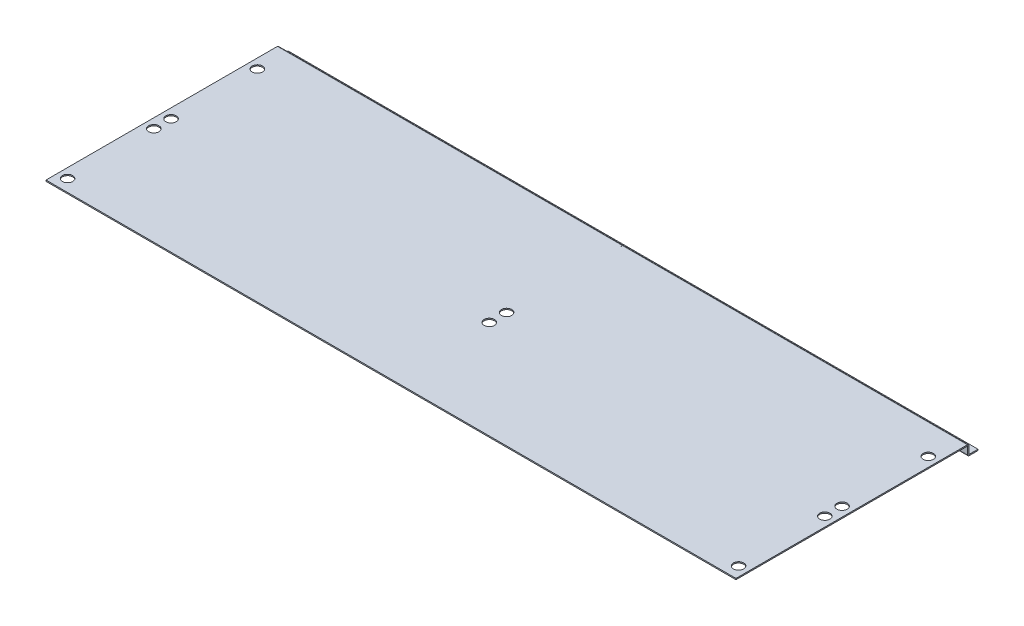
SolidWorks part; units mm, degrees
note: The reader was unsure of these and kept them because the rebuilt part matched: flange length of "边线-法兰1", "边线-法兰2".
material "1023 碳钢板 (SS)"
ref_plane "前视基准面" through (0, 0, 0) normal (0, 0, 1) x (1, 0, 0)
ref_plane "上视基准面" through (0, 0, 0) normal (0, 1, 0) x (1, 0, 0)
ref_plane "右视基准面" through (0, 0, 0) normal (1, 0, 0) x (0, 0, -1)
sketch "草图1" plane through (0, 0, 0) normal (0, 1, 0) x (1, 0, 0)
  line L0 (0, 67.5) -> (0, -67.5) construction
  line L1 (-200, 67.5) -> (200, 67.5)
  line L2 (-200, 67.5) -> (-200, -67.5)
  line L3 (-200, -67.5) -> (200, -67.5)
  line L4 (200, 67.5) -> (200, -67.5)
  line L5 (-200, 67.5) -> (200, -67.5) construction
  line L6 (-200, -67.5) -> (200, 67.5) construction
  circle A0 centre (-194.5, -60.5) radius 3
  circle A1 centre (-194.5, -10.5) radius 3
  circle A2 centre (-194.5, -0.5) radius 3
  circle A3 centre (-194.5, 49.5) radius 3
  circle A8 centre (0, -10.5) radius 3
  circle A9 centre (0, -0.5) radius 3
  circle A10 centre (194.5, -60.5) radius 3
  circle A11 centre (194.5, -10.5) radius 3
  circle A12 centre (194.5, -0.5) radius 3
  circle A13 centre (194.5, 49.5) radius 3
  point P0 (0, 0)
  point P28 (0, 0)
  point P29 (0, 0)
  dimension "D4" = 7
  dimension "D5" = 6
  dimension "D6" = 5.5
  dimension "D7" = 5.5
  dimension "D8" = 5.5
  dimension "D1" = 400
  dimension "D2" = 135
  dimension "D3" = 5.5
  dimension "D9" = 50
  dimension "D10" = 10
  dimension "D11" = 50
  dimension "D12" = 18
base flange "基体-法兰1" sketch "草图1" thickness 0.7 reverse thickness direction no parameters "D1"=0.2
edge flange "边线-法兰1" sketch "草图10" flange angle 90 flange length 6 flange position material inside bend radius 0.2 thickness 0.7 relief rectangular parameters "D6"=10
sketch "草图10" plane through (0, -0.7, -67.5) normal (0, 0, -1) x (1, 0, 0)
  line L0 (200, 0) -> (-200, 0) construction
  line L1 (200, 0) -> (-200, 0)
  line L2 (-200, 0) -> (-200, 5.3)
  line L3 (-200, 5.3) -> (200, 5.3)
  line L4 (200, 5.3) -> (200, 0)
bend "边线折弯1" bend radius 0.2 bend angle 90 parameters "D5"=1
edge flange "边线-法兰2" sketch "草图13" flange angle 90 flange length 6 flange position material inside bend radius 0.2 thickness 0.7 relief rectangular parameters "D6"=10
sketch "草图13" plane through (0, -6, -67.5) normal (0, -1, 0) x (-1, 0, 0)
  line L2 (-200, 0) -> (-200, 5.3)
  line L3 (-200, 5.3) -> (200, 5.3)
  line L4 (200, 5.3) -> (200, 0)
  line L7 (-200, 0) -> (200, 0) construction
  line L8 (-200, 0) -> (200, 0)
bend "边线折弯2" bend radius 0.2 bend angle 90 parameters "D5"=2
sketch "折弯-线1" plane through (0, 0, 0) normal (0, 1, 0) x (1, 0, 0)
sketch "边界框1" plane through (0, 0, 0) normal (0, 1, 0) x (1, 0, 0)
sheet metal parameters "钣金6" thickness 0.7 parameters "D1"=0.2
flat pattern "平板型式6" [suppressed]
sketch "折弯-线2" plane through (0, 0, 0) normal (0, 1, 0) x (1, 0, 0)
sketch "边界框2" [suppressed] plane through (0, 0, 0) normal (0, 1, 0) x (1, 0, 0)
sheet metal parameters "钣金7" thickness 0.7 parameters "D1"=0.2
flat pattern "平板型式6" [suppressed]
sketch "折弯-线2" plane through (0, 0, 0) normal (0, 1, 0) x (1, 0, 0)
sketch "边界框2" [suppressed] plane through (0, 0, 0) normal (0, 1, 0) x (1, 0, 0)
bend of the flat pattern "展平-<边线折弯1>1"
sheet metal parameters "钣金8" thickness 0.7 parameters "D1"=0.2
flat pattern "平板型式6" [suppressed]
sketch "折弯-线2" plane through (0, 0, 0) normal (0, 1, 0) x (1, 0, 0)
sketch "边界框2" [suppressed] plane through (0, 0, 0) normal (0, 1, 0) x (1, 0, 0)
bend of the flat pattern "展平-<边线折弯1>1"
bend of the flat pattern "展平-<边线折弯2>1"
